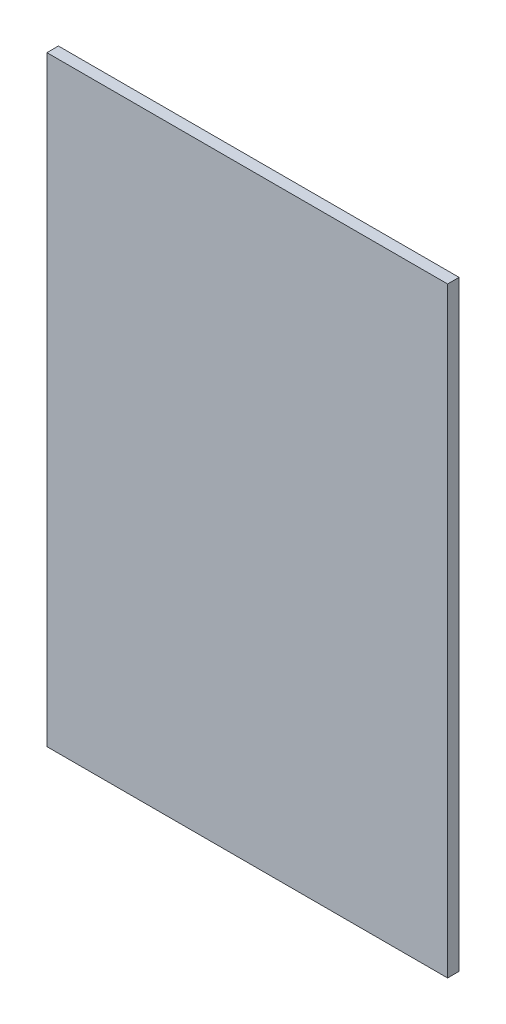
SolidWorks part; units mm, degrees
material "Cedar"
ref_plane "Front Plane" through (0, 0, 0) normal (0, 0, 1) x (1, 0, 0)
ref_plane "Top Plane" through (0, 0, 0) normal (0, 1, 0) x (1, 0, 0)
ref_plane "Right Plane" through (0, 0, 0) normal (1, 0, 0) x (0, 0, -1)
sketch "Sketch1" plane through (0, 0, 0) normal (0, 0, 1) x (1, 0, 0)
  line L1 (-304.8, -457.2) -> (304.8, -457.2)
  line L2 (-304.8, -457.2) -> (-304.8, 457.2)
  line L3 (-304.8, 457.2) -> (304.8, 457.2)
  line L4 (304.8, -457.2) -> (304.8, 457.2)
  line L5 (-304.8, -457.2) -> (304.8, 457.2) construction
  line L6 (-304.8, 457.2) -> (304.8, -457.2) construction
  point P0 (0, 0)
  dimension "D1" = 609.6
  dimension "D2" = 914.4
extrude "Boss-Extrude1" add sketch "Sketch1" along normal blind 17.4752
